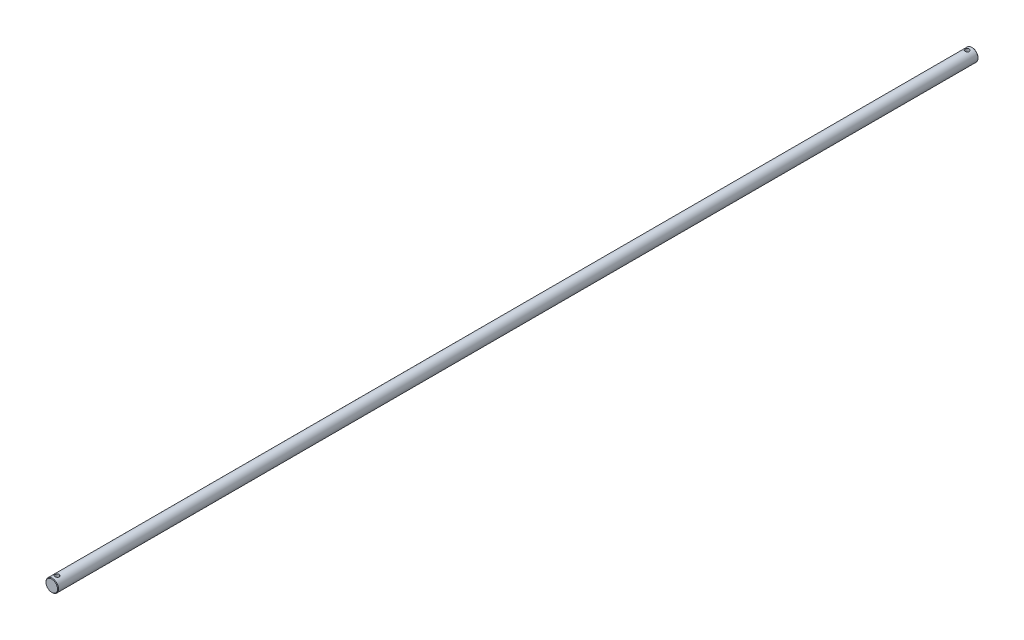
SolidWorks part; units mm, degrees
material "1.0037 (S235JR)"
ref_plane "Płaszczyzna przednia" through (0, 0, 0) normal (0, 0, 1) x (1, 0, 0)
ref_plane "Płaszczyzna górna" through (0, 0, 0) normal (0, 1, 0) x (1, 0, 0)
ref_plane "Płaszczyzna prawa" through (0, 0, 0) normal (1, 0, 0) x (0, 0, -1)
sketch "Szkic1" plane through (0, 0, 0) normal (0, 0, 1) x (1, 0, 0)
  circle A0 centre (0, 0) radius 12
  dimension "D1" = 24
extrude "Dodanie-wyciągnięcie1" add sketch "Szkic1" along normal blind 880 and the other way blind 880
sketch "Szkic2" plane through (0, 0, 0) normal (0, 1, 0) x (1, 0, 0)
  line L0 (12, 880) -> (-12, 880) construction
  line L1 (-12, -880) -> (12, -880) construction
  circle A0 centre (0, 870) radius 4
  circle A1 centre (0, -870) radius 4
  dimension "D1" = 8
  dimension "D3" = 8
  dimension "D2" = 10
  dimension "D4" = 10
extrude "Wytnij-wyciągnięcie1" cut sketch "Szkic2" against normal up to next and the other way up to next
chamfer "Sfazowanie1" distance 1 angle 45 2 edges at (12, 0, -880) (12, 0, 880)
